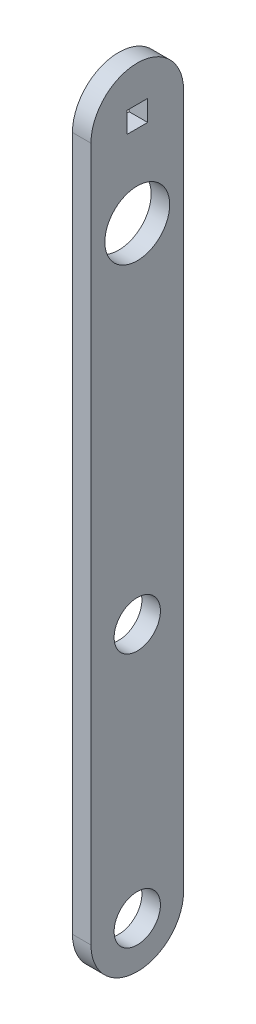
SolidWorks part; units mm, degrees
ref_plane "Front Plane" through (0, 0, 0) normal (0, 0, 1) x (1, 0, 0)
ref_plane "Top Plane" through (0, 0, 0) normal (0, 1, 0) x (1, 0, 0)
ref_plane "Right Plane" through (0, 0, 0) normal (1, 0, 0) x (0, 0, -1)
sketch "Sketch2" plane through (0, 0, 0) normal (1, 0, 0) x (0, 0, -1)
  line L0 (-20, 0) -> (20, 0) construction
  line L1 (-20, 40) -> (-20, -260)
  line L2 (20, 40) -> (20, -260)
  line L3 (0, 0) -> (0, 40) construction
  line L4 (20, 40) -> (-20, 40) construction
  line L5 (-4.5, 35.5) -> (4.5, 35.5)
  line L6 (-4.5, 35.5) -> (-4.5, 44.5)
  line L7 (-4.5, 44.5) -> (4.5, 44.5)
  line L8 (4.5, 35.5) -> (4.5, 44.5)
  line L9 (-4.5, 35.5) -> (4.5, 44.5) construction
  line L10 (-4.5, 44.5) -> (4.5, 35.5) construction
  line L11 (-20, -260) -> (20, -260) construction
  line L12 (0, 0) -> (0, -150) construction
  circle A0 centre (0, 0) radius 14
  arc A1 (-20, 40) -> (20, 40) centre (0, 40) cw
  circle A2 centre (0, -150) radius 10
  arc A3 (-20, -260) -> (20, -260) centre (0, -260) ccw
  circle A4 centre (0, -260) radius 10
  dimension "D1" = 28
  dimension "D7" = 20
  dimension "D8" = 20
  dimension "D2" = 40
  dimension "D3" = 40
  dimension "D4" = 9
  dimension "D5" = 300
  dimension "D6" = 150
extrude "Boss-Extrude1" add sketch "Sketch2" along normal blind 4 and the other way blind 4 contours L1 A3 L2 A1 L8 L5 L6 L7 A0 A2 region at (0, -111.6924, 0)
